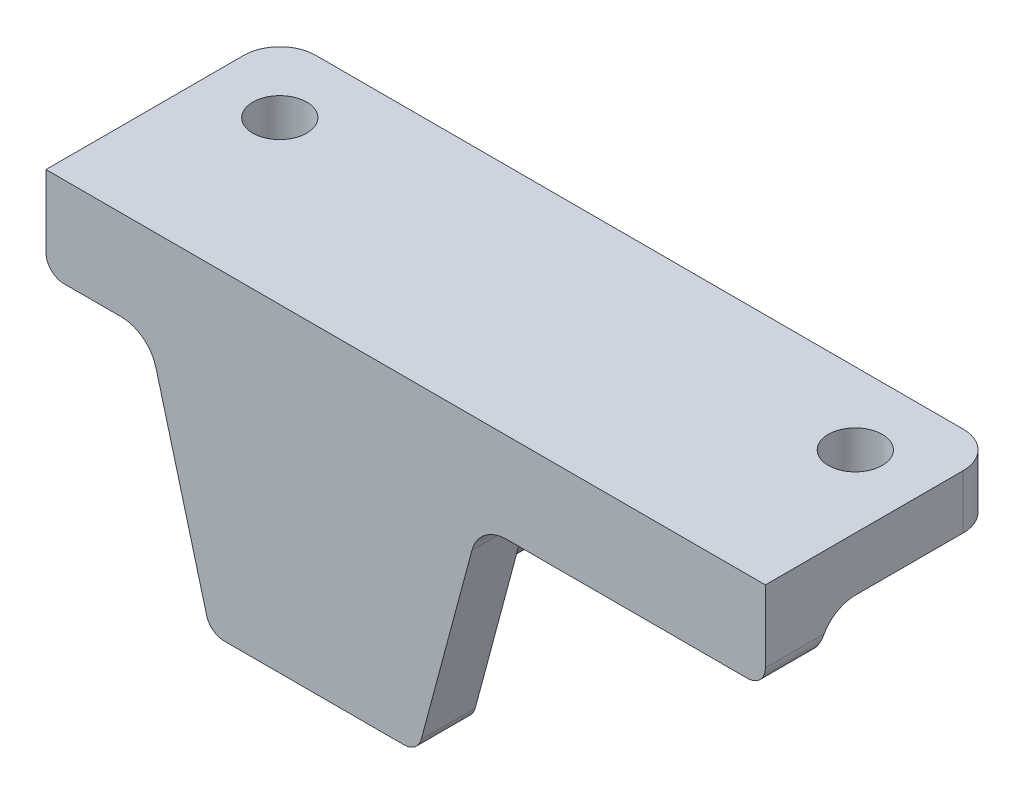
SolidWorks part; units mm, degrees
ref_plane "Front Plane" through (0, 0, 0) normal (0, 0, 1) x (1, 0, 0)
ref_plane "Top Plane" through (0, 0, 0) normal (0, 1, 0) x (1, 0, 0)
ref_plane "Right Plane" through (0, 0, 0) normal (1, 0, 0) x (0, 0, -1)
sketch "Sketch1" plane through (0, 0, 0) normal (0, 0, 1) x (1, 0, 0)
  line L1 (-15.9, -6.25) -> (15.9, -6.25)
  line L2 (-15.9, -6.25) -> (-15.9, 6.25)
  line L3 (-15.9, 6.25) -> (15.9, 6.25)
  line L4 (15.9, -6.25) -> (15.9, 6.25)
  line L5 (-15.9, -6.25) -> (15.9, 6.25) construction
  line L6 (-15.9, 6.25) -> (15.9, -6.25) construction
  line L7 (11.7, -6.25) -> (-11.7, -6.25)
  line L8 (11.7, -6.25) -> (11.7, 6.25)
  line L9 (11.7, 6.25) -> (-11.7, 6.25)
  line L10 (-11.7, -6.25) -> (-11.7, 6.25)
  line L11 (11.7, -6.25) -> (-11.7, 6.25) construction
  line L12 (11.7, 6.25) -> (-11.7, -6.25) construction
  circle A0 centre (-14.4, 0) radius 1
  circle A1 centre (-14.4, 3.5) radius 1
  circle A2 centre (-14.4, -3.5) radius 1
  circle A3 centre (14.4, 0) radius 1
  circle A4 centre (14.4, 3.5) radius 1
  circle A5 centre (14.4, -3.5) radius 1
  point P0 (0, 0)
  point P20 (0, 0)
  dimension "D3" = 2
  dimension "D1" = 31.8
  dimension "D2" = 12.5
  dimension "D4" = 1.5
  dimension "D5" = 3.5
  dimension "D6" = 3.5
  dimension "D7" = 1.5
  dimension "D8" = 23.4
sketch "Sketch3" plane through (0, 0, 0) normal (0, 0, 1) x (1, 0, 0)
  line L2 (-0.1, -6) -> (-10.1, -6)
  line L3 (-11.0659, -5.2588) -> (-13.8865, 5.2676)
  line L7 (0.8659, -5.2588) -> (3.6865, 5.2676)
  line L12 (-20, 11.75) -> (20, 11.75)
  line L14 (-15.8183, 6.75) -> (-19, 6.75)
  line L15 (-20, 7.75) -> (-20, 11.75)
  line L16 (5.6183, 6.75) -> (19, 6.75)
  line L17 (20, 7.75) -> (20, 11.75)
  arc A3 (-10.1, -6) -> (-11.0659, -5.2588) centre (-10.1, -5) cw
  arc A5 (0.8659, -5.2588) -> (-0.1, -6) centre (-0.1, -5) cw
  arc A8 (-13.8865, 5.2676) -> (-15.8183, 6.75) centre (-15.8183, 4.75) ccw
  arc A9 (5.6183, 6.75) -> (3.6865, 5.2676) centre (5.6183, 4.75) ccw
  arc A10 (-19, 6.75) -> (-20, 7.75) centre (-19, 7.75) cw
  arc A11 (20, 7.75) -> (19, 6.75) centre (19, 7.75) cw
  circle A12 centre (0, 0) radius 3.5 construction
  point P1 (0, 11.75)
  point P2 (-5.1, -6)
  point P25 (-13.8476, -6)
  point P46 (-14.2837, 6.75)
  point P49 (4.0837, 6.75)
  dimension "D9" = 14.9
  dimension "D10" = 1
  dimension "D6" = 1
  dimension "D14" = 2
  dimension "D15" = 2
  dimension "D16" = 1
  dimension "D17" = 1
  dimension "D20" = 7
  dimension "D3" = 75
  dimension "D4" = 6
  dimension "D5" = 11.75
  dimension "D7" = 75
  dimension "D8" = 10
  dimension "D18" = 40
  dimension "D19" = 5
extrude "Boss-Extrude1" add sketch "Sketch3" along normal blind 3
sketch "Sketch4" plane through (0, 0, 0) normal (0, 0, -1) x (-1, 0, 0)
  line L2 (20, 11.75) -> (20, 7.75) construction
  line L3 (-20, 11.75) -> (20, 11.75)
  line L4 (-20, 11.75) -> (-20, 8.75)
  line L5 (-20, 8.75) -> (20, 8.75)
  line L6 (20, 11.75) -> (20, 8.75)
  point P9 (-20, 8.75)
  point P12 (20, 8.75)
  dimension "D1" = 3
extrude "Boss-Extrude2" add sketch "Sketch4" along normal blind 10
fillet "Fillet1" radius 2 1 edges at (0, 8.75, 0)
fillet "Fillet2" radius 2 2 edges at (-20, 10.25, -10) (20, 10.25, -10)
sketch "Sketch5" plane through (0, 8.75, 0) normal (0, -1, 0) x (1, 0, 0)
  line L0 (-20, -8) -> (-20, -2) construction
  line L2 (18, -10) -> (-18, -10) construction
  circle A0 centre (-16, -6) radius 1.5
  dimension "D1" = 3
  dimension "D2" = 4
  dimension "D3" = 4
extrude "Cut-Extrude1" cut sketch "Sketch5" against normal through all
mirror "Mirror1" about plane through (0, 0, 0) normal (1, 0, 0) of "Cut-Extrude1"
sketch "Sketch6" plane through (0, 0, 0) normal (0, 0, -1) x (-1, 0, 0)
  line L0 (20, 11.75) -> (20, 8.75) construction
  circle A0 centre (5.1, 0) radius 3.5
  dimension "D1" = 7
  dimension "D2" = 14.9
extrude "Boss-Extrude3" add sketch "Sketch6" along normal blind 16
ref_plane "Plane3" through (-8.6, 0, 0) normal (-1, 0, 0) x (0, 0, 1)
ref_plane "Plane4" through (-1.6, 0, 0) normal (1, 0, 0) x (0, 0, -1)
ref_plane "Plane5" through (-5.1, 0, 0) normal (1, 0, 0) x (0, 0, -1)
fillet "Fillet3" radius 0.5 1 edges at (-8.6, 0, -16)
sketch "Sketch7" plane through (-5.1, 0, 0) normal (1, 0, 0) x (0, 0, -1)
  line L0 (8, 8.75) -> (2, 8.75) construction
  line L1 (0, 0) -> (10, 0)
  line L2 (0, 0) -> (0, 8.75)
  line L3 (0, 8.75) -> (10, 8.75)
  line L4 (10, 0) -> (10, 8.75)
  line L5 (10, 11.75) -> (10, 8.75) construction
extrude "Boss-Extrude4" add sketch "Sketch7" along normal mid plane 3 contours L4 L3 L2 L1
fillet "Fillet4" radius 1 9 edges at (-5.1, 3.5, -10) (-6.6, 8.75, -6) (-6.6, 8.1642, -0.5858) (-3.6, 8.75, -6) (-3.6, 8.1642, -0.5858) (-6.6, 3.1623, -5) (-3.6, 3.1623, -5) (-6.6, 4.9561, 0) (-3.6, 4.9561, 0)
equation "\"D6@Sketch1\"=\"D5@Sketch1\""
equation "\"D7@Sketch1\"=\"D4@Sketch1\""
